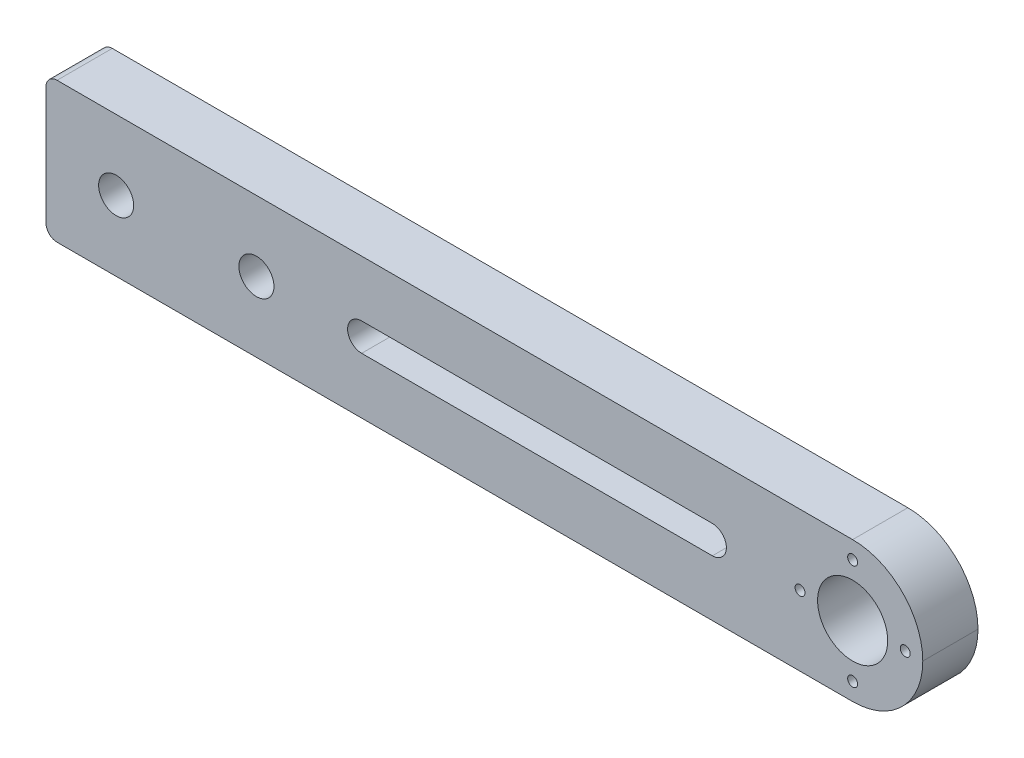
SolidWorks part; units mm, degrees
ref_plane "Front Plane" through (0, 0, 0) normal (0, 0, 1) x (1, 0, 0)
ref_plane "Top Plane" through (0, 0, 0) normal (0, 1, 0) x (1, 0, 0)
ref_plane "Right Plane" through (0, 0, 0) normal (1, 0, 0) x (0, 0, -1)
sketch "Sketch1" plane through (0, 0, 0) normal (0, 0, 1) x (1, 0, 0)
  line L0 (-60.325, 0) -> (-73.025, 0) construction
  line L2 (-73.025, -12.7) -> (-73.025, 12.7)
  line L4 (73.025, -12.7) -> (73.025, 12.7) construction
  line L5 (-73.025, -12.7) -> (73.025, 12.7) construction
  line L6 (-73.025, 12.7) -> (73.025, -12.7) construction
  line L7 (-15.875, 0) -> (47.625, 0) construction
  line L8 (-15.875, 2.54) -> (47.625, 2.54)
  line L9 (-15.875, -2.54) -> (47.625, -2.54)
  line L12 (73.025, 9.525) -> (73.025, -9.525) construction
  line L18 (63.5, 0) -> (82.55, 0) construction
  line L19 (-60.325, 0) -> (-34.925, 0) construction
  line L20 (73.025, -12.7) -> (-73.025, -12.7)
  line L21 (73.025, 12.7) -> (-73.025, 12.7)
  line L22 (73.025, -12.7) -> (85.725, -12.7)
  line L23 (85.725, -12.7) -> (85.725, 12.7)
  line L24 (85.725, 12.7) -> (73.025, 12.7)
  circle A0 centre (-60.325, 0) radius 3.175
  arc A1 (-15.875, 2.54) -> (-15.875, -2.54) centre (-15.875, 0) ccw
  arc A2 (47.625, -2.54) -> (47.625, 2.54) centre (47.625, 0) ccw
  circle A6 centre (73.025, 0) radius 6.35
  circle A8 centre (73.025, 9.525) radius 0.9
  circle A9 centre (73.025, -9.525) radius 0.9
  circle A10 centre (63.5, 0) radius 0.9
  circle A11 centre (82.55, 0) radius 0.9
  circle A12 centre (-34.925, 0) radius 3.175
  point P0 (0, 0)
  point P11 (15.875, 0)
  point P23 (73.025, 0)
  point P24 (73.025, 0)
  dimension "D4" = 6.35
  dimension "D7" = 1.8
  dimension "D8" = 12.7
  dimension "D10" = 19.05
  dimension "D2" = 25.4
  dimension "D3" = 12.7
  dimension "D5" = 5.08
  dimension "D6" = 63.5
  dimension "D9" = 19.05
  dimension "D11" = 44.45
  dimension "D12" = 25.4
  dimension "D13" = 25.4
  dimension "D14" = 12.7
  dimension "D15" = 158.75
extrude "Boss-Extrude1" add sketch "Sketch1" along normal blind 10
fillet "Fillet2" radius 2 2 edges at (-73.025, -12.7, 5) (-73.025, 12.7, 5)
fillet "Fillet3" radius 12.7 2 edges at (85.725, 12.7, 5) (85.725, -12.7, 5)
